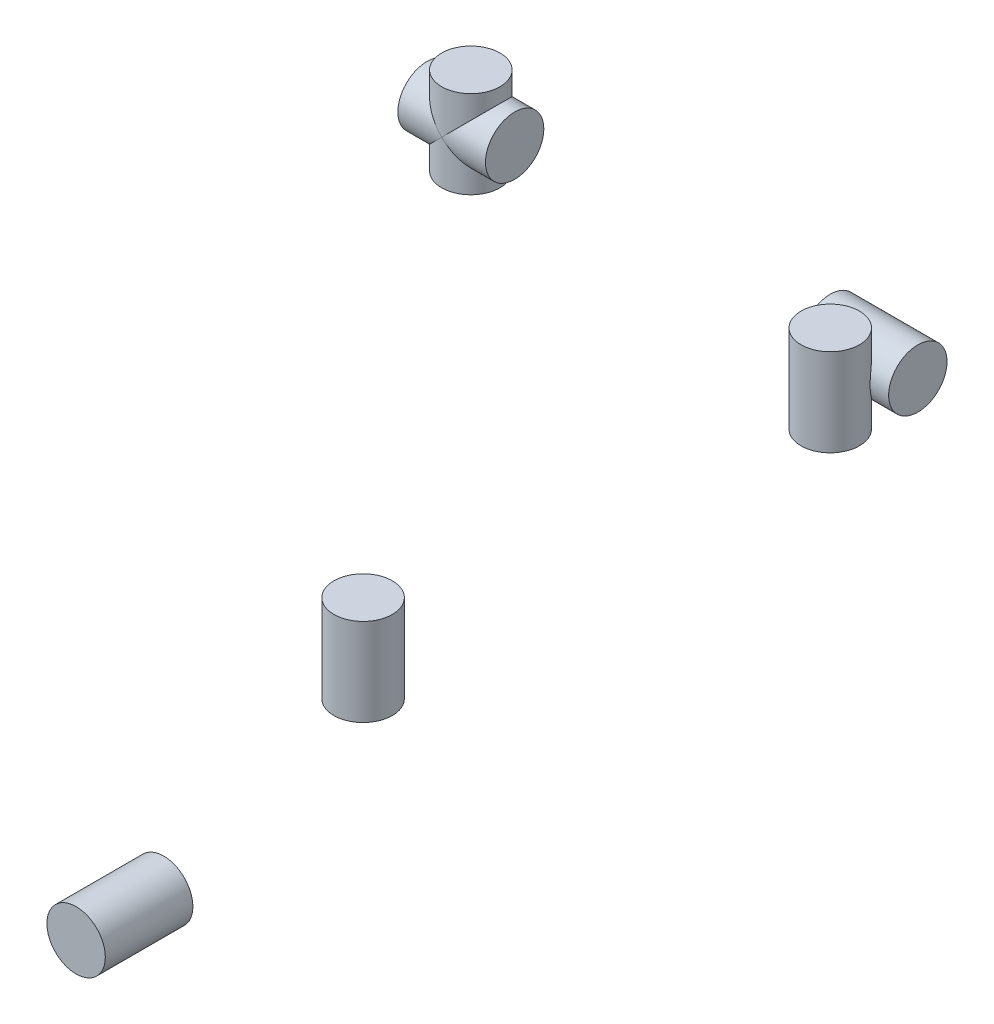
SolidWorks part; units mm, degrees
ref_plane "Front Plane" through (0, 0, 0) normal (0, 0, 1) x (1, 0, 0)
ref_plane "Top Plane" through (0, 0, 0) normal (0, 1, 0) x (1, 0, 0)
ref_plane "Right Plane" through (0, 0, 0) normal (1, 0, 0) x (0, 0, -1)
sketch "Sketch1" plane through (0, 0, 0) normal (0, 1, 0) x (1, 0, 0)
  line L0 (0, 0) -> (0, 135.8) construction
  line L1 (0, 135.8) -> (-37.5, 135.8) construction
  line L2 (-37.5, 135.8) -> (-37.5, 295.8) construction
  line L3 (-37.5, 295.8) -> (-37.5, 310.8) construction
  line L4 (-37.5, 310.8) -> (-175.6, 310.8) construction
  line L5 (-175.6, 310.8) -> (-203.8, 310.8) construction
  point P8 (0, 0)
  point P9 (0, 0)
  point P10 (0, 0)
  point P11 (0, 0)
  dimension "D1" = 135.8
  dimension "D2" = 160
  dimension "D3" = 15
  dimension "D4" = 37.5
  dimension "D5" = 138.1
  dimension "D6" = 28.2
sketch "Sketch2" plane through (0, 0, 0) normal (0, 0, 1) x (1, 0, 0)
  circle A0 centre (0, 0) radius 10
  dimension "D1" = 20
extrude "Boss-Extrude1" add sketch "Sketch2" against normal blind 30
sketch "Sketch4" plane through (0, 0, 0) normal (0, 1, 0) x (1, 0, 0)
  circle A0 centre (-37.5, 135.8) radius 10
  circle A1 centre (-37.5, 295.8) radius 10
  circle A2 centre (-175.6, 310.8) radius 10
  dimension "D1" = 20
  dimension "D2" = 20
  dimension "D3" = 20
extrude "Boss-Extrude3" add sketch "Sketch4" along normal blind 15 and the other way blind 15 separate body
ref_plane "Plane1" through (-37.5, 0, 0) normal (1, 0, 0) x (0, 0, -1)
sketch "Sketch5" plane through (-37.5, 0, 0) normal (1, 0, 0) x (0, 0, -1)
  line L0 (295.8, 0) -> (310.8, 0) construction
  circle A0 centre (310.8, 0) radius 10
  dimension "D1" = 20
extrude "Boss-Extrude4" add sketch "Sketch5" along normal blind 15 and the other way blind 15
ref_plane "Plane2" through (-175.6, 0, 0) normal (1, 0, 0) x (0, 0, -1)
sketch "Sketch6" plane through (-175.6, 0, 0) normal (1, 0, 0) x (0, 0, -1)
  circle A0 centre (310.8, 0) radius 10
extrude "Boss-Extrude5" add sketch "Sketch6" along normal blind 15 and the other way blind 15
